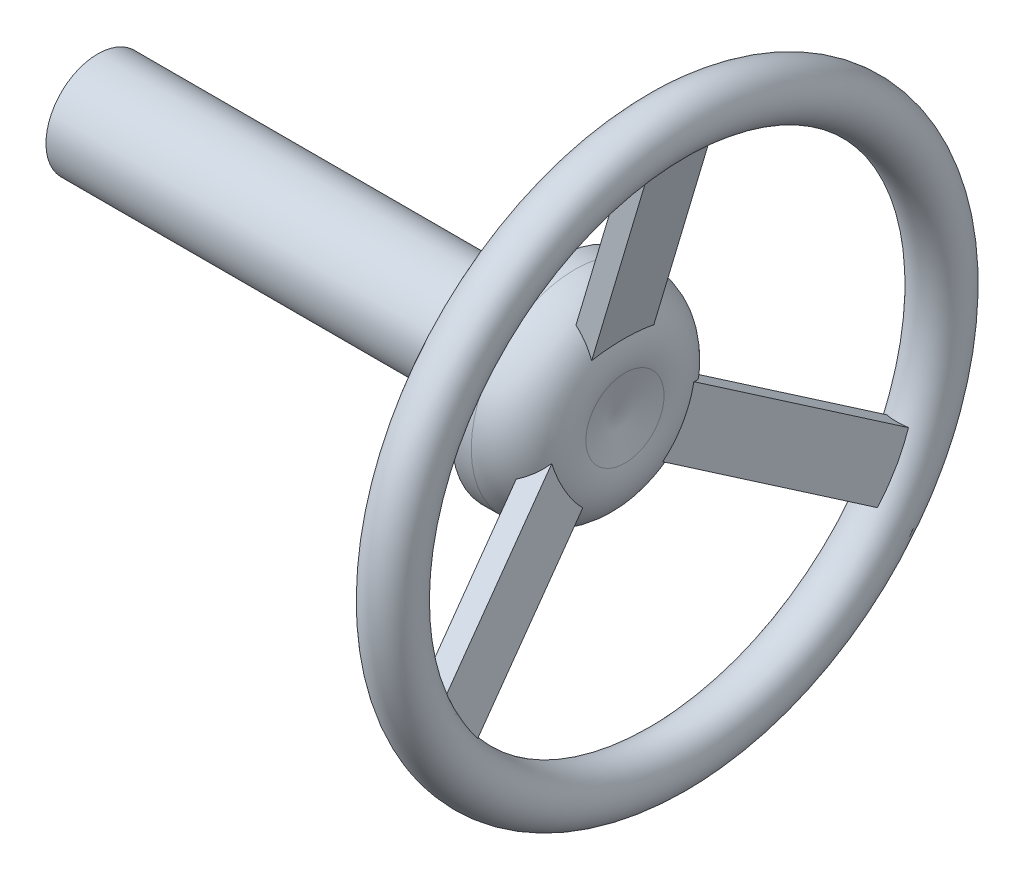
SolidWorks part; units mm, degrees
ref_plane "Front Plane" through (0, 0, 0) normal (0, 0, 1) x (1, 0, 0)
ref_plane "Top Plane" through (0, 0, 0) normal (0, 1, 0) x (1, 0, 0)
ref_plane "Right Plane" through (0, 0, 0) normal (1, 0, 0) x (0, 0, -1)
sketch "Sketch1" plane through (0, 0, 0) normal (0, 0, 1) x (1, 0, 0)
  line L0 (0, 0) -> (-49.9651, 0) construction
  line L1 (-49.9651, 0) -> (-49.9651, 5)
  line L2 (-49.9651, 5) -> (-9.9651, 5)
  line L3 (-9.9651, 5) -> (-5.7696, 10)
  line L4 (-5.7696, 10) -> (2.5304, 10)
  line L5 (2.5304, 10) -> (0, 0)
  line L6 (0, 0) -> (-49.9651, 0)
  dimension "D1" = 5
  dimension "D2" = 40
  dimension "D3" = 8.3
  dimension "D4" = 130
  dimension "D5" = 10
  dimension "D6" = 75.8
revolve "Revolve1" add sketch "Sketch1" angle 360 about L0
sketch "Sketch2" plane through (0, 0, 0) normal (0, 0, 1) x (1, 0, 0)
  line L0 (-49.9651, 5) -> (-49.9651, -5) construction
  line L1 (-49.9651, -5) -> (-9.9651, -5) construction
  line L2 (0, 0) -> (21.6162, 0) construction
  circle A0 centre (5.0349, 26.5) radius 2.5
  dimension "D3" = 5
  dimension "D1" = 55
  dimension "D2" = 31.5
revolve "Revolve2" add sketch "Sketch2" angle 360 about L2
sketch "Sketch3" plane through (0, 0, 0) normal (0, 0, 1) x (1, 0, 0)
  line L0 (-0.5416, 9.2) -> (1.6349, 9.2)
  line L1 (1.6349, 9.2) -> (6.1292, 24.3309)
  line L2 (6.1292, 24.3309) -> (4.1292, 24.9249)
  line L3 (4.1292, 24.9249) -> (-0.5416, 9.2)
extrude "Boss-Extrude1" add sketch "Sketch3" along normal mid plane 6
pattern_circular "CirPattern1" count 3 over 360 about axis through (2.5304, 0, 0) along (1, 0, 0) of "Boss-Extrude1"
fillet "Fillet1" radius 5 1 edges at (2.5304, 10, 0)
